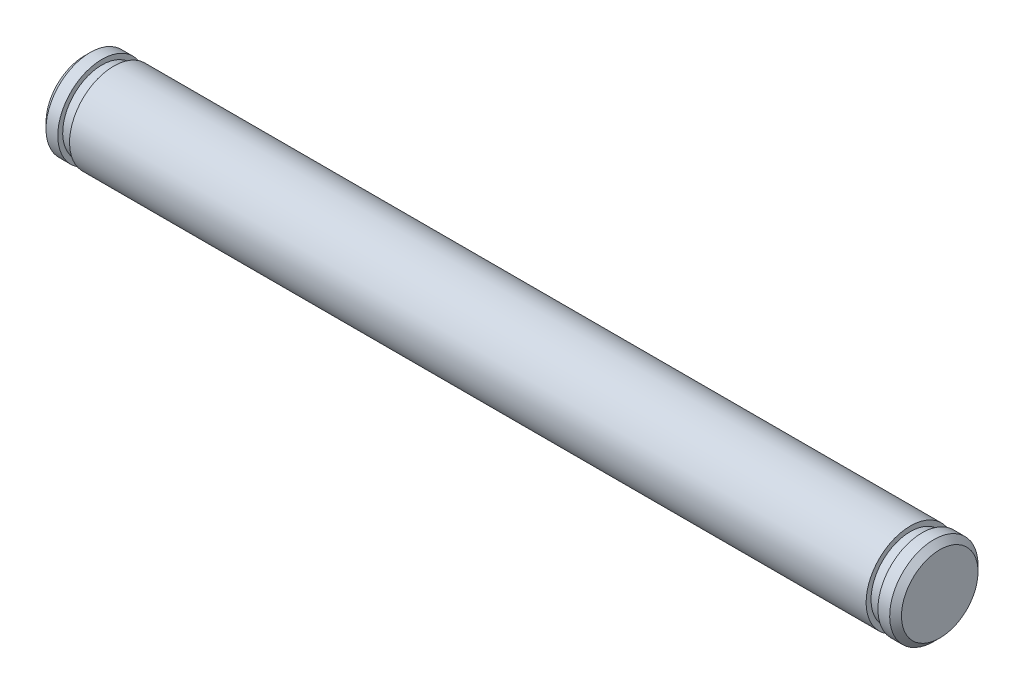
SolidWorks part; units mm, degrees
material "AISI 1020"
ref_plane "Front" through (0, 0, 0) normal (0, 0, 1) x (1, 0, 0)
ref_plane "Top" through (0, 0, 0) normal (0, 1, 0) x (1, 0, 0)
ref_plane "Right" through (0, 0, 0) normal (1, 0, 0) x (0, 0, -1)
ref_axis "side-side" through (80.9, 0, 0) along (-1, 0, 0)
ref_axis "up-down" through (0, 50, 0) along (0, -1, 0)
ref_axis "front-back" through (0, 0, -80.9) along (0, 0, 1)
sketch "Sketch1" plane through (0, 0, 0) normal (0, 0, 1) x (1, 0, 0)
  line L0 (-2, 0) -> (-12.9928, 0) construction
  line L1 (-2, 0) -> (56.102, 0)
  line L2 (-2, 0) -> (-2, 3)
  line L3 (-2, 3) -> (-0.8, 3)
  line L4 (56.102, 0) -> (56.102, 3)
  line L5 (0, 3) -> (54.102, 3)
  line L6 (54.902, 3) -> (56.102, 3)
  line L7 (-0.8, 3) -> (-0.8, 2.667)
  line L8 (-0.8, 2.667) -> (0, 2.667)
  line L9 (0, 3) -> (0, 2.667)
  line L11 (54.102, 3) -> (54.102, 2.667)
  line L12 (54.102, 2.667) -> (54.902, 2.667)
  line L13 (54.902, 3) -> (54.902, 2.667)
  point P10 (-0.4, 2.667)
  dimension "D1" = 6
  dimension "D2" = 5.334
  dimension "D3" = 0.8
  dimension "D4" = 1.2
  dimension "D5" = 54.102
revolve "Revolve1" add sketch "Sketch1" angle 360 about L0
chamfer "Chamfer1" distance 0.4 angle 45 2 edges at (-2, 3, 0) (56.102, 3, 0)
